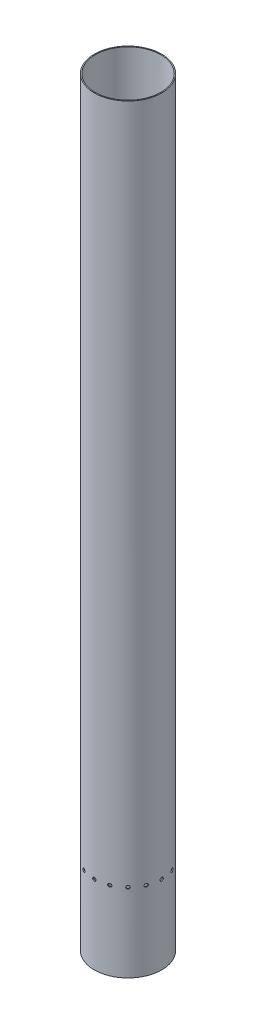
SolidWorks part; units mm, degrees
ref_plane "Front Plane" through (0, 0, 0) normal (0, 0, 1) x (1, 0, 0)
ref_plane "Top Plane" through (0, 0, 0) normal (0, 1, 0) x (1, 0, 0)
ref_plane "Right Plane" through (0, 0, 0) normal (1, 0, 0) x (0, 0, -1)
sketch "Sketch1" plane through (0, 0, 0) normal (0, 1, 0) x (1, 0, 0)
  circle A0 centre (0, 0) radius 63.5
  circle A1 centre (0, 0) radius 65.405
  dimension "D1" = 127
  dimension "D2" = 130.81
extrude "Boss-Extrude1" add sketch "Sketch1" against normal blind 1473.2
ref_plane "Plane1" through (0, 0, 65.405) normal (0, 0, 1) x (1, 0, 0)
ref_axis "Axis1" through (0, -1473.2, 0) along (0, 1, 0)
sketch "Sketch2" plane through (0, 0, 65.405) normal (0, 0, 1) x (1, 0, 0)
  line L0 (-65.405, -1473.2) -> (65.405, -1473.2) construction
  circle A0 centre (0, -1320.8) radius 3.175
  dimension "D1" = 6.35
  dimension "D2" = 152.4
extrude "Cut-Extrude1" cut sketch "Sketch2" against normal up to next contours A0
pattern_circular "CirPattern1" count 16 over 360 about axis through (0, -1473.2, 0) along (0, 1, 0) of "Cut-Extrude1"
